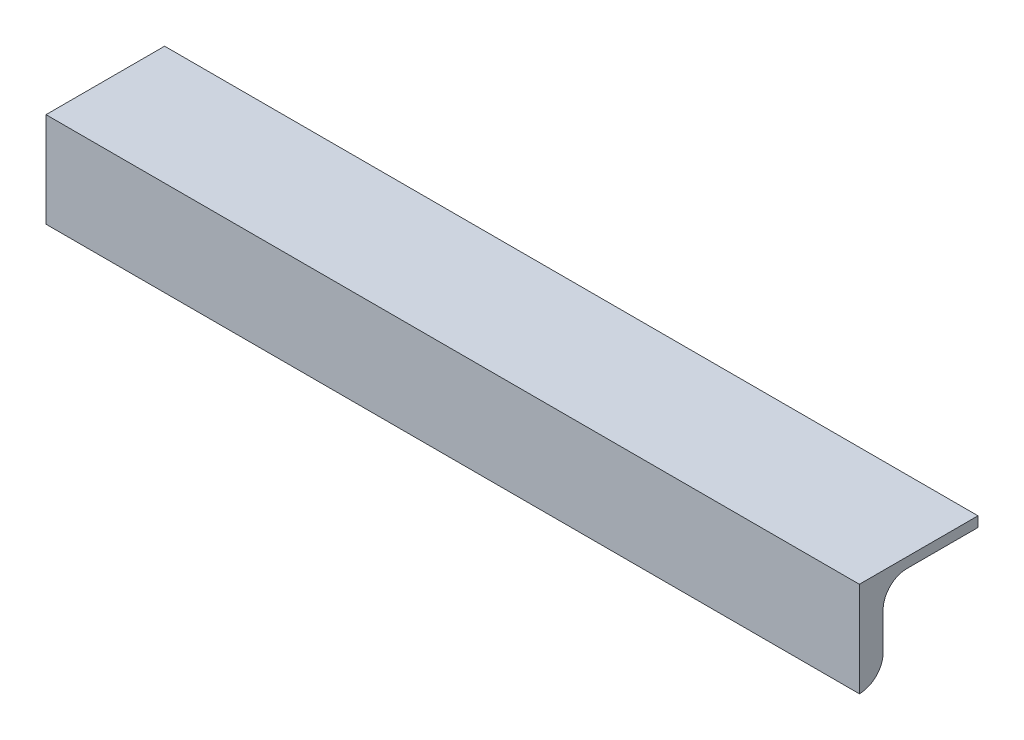
SolidWorks part; units mm, degrees
ref_plane "Front Plane" through (0, 0, 0) normal (0, 0, 1) x (1, 0, 0)
ref_plane "Top Plane" through (0, 0, 0) normal (0, 1, 0) x (1, 0, 0)
ref_plane "Right Plane" through (0, 0, 0) normal (1, 0, 0) x (0, 0, -1)
sketch "Sketch1" plane through (0, 0, 0) normal (0, 1, 0) x (1, 0, 0)
  line L1 (-120, 17.5) -> (120, 17.5)
  line L2 (-120, 17.5) -> (-120, -17.5)
  line L3 (-120, -17.5) -> (120, -17.5)
  line L4 (120, 17.5) -> (120, -17.5)
  line L5 (0, -17.5) -> (0, 17.5) construction
  line L6 (-120, 0) -> (120, 0) construction
  point P0 (0, 0)
  dimension "D1" = 35
  dimension "D2" = 240
extrude "Boss-Extrude1" add sketch "Sketch1" along normal blind 3
sketch "Sketch3" plane through (0, 0, 0) normal (0, -1, 0) x (1, 0, 0)
  line L0 (-120, -17.5) -> (-120, 17.5) construction
  line L1 (120, 17.5) -> (-120, 17.5)
  line L2 (120, 17.5) -> (120, 10.5)
  line L3 (120, 10.5) -> (-120, 10.5)
  line L4 (-120, 17.5) -> (-120, 10.5)
  line L5 (0, 10.5) -> (0, 17.5) construction
  line L6 (120, 14) -> (-120, 14) construction
  point P452 (0, 14)
  dimension "D1" = 7
extrude "Boss-Extrude3" add sketch "Sketch3" along normal blind 25
fillet "Fillet1" radius 7 2 edges at (0, 0, 10.5) (0, -25, 10.5)
